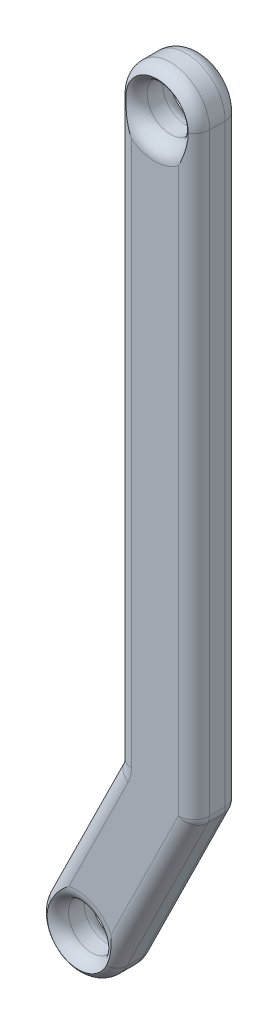
SolidWorks part; units mm, degrees
ref_plane "Front Plane" through (0, 0, 0) normal (0, 0, 1) x (1, 0, 0)
ref_plane "Top Plane" through (0, 0, 0) normal (0, 1, 0) x (1, 0, 0)
ref_plane "Right Plane" through (0, 0, 0) normal (1, 0, 0) x (0, 0, -1)
sketch "Sketch1" plane through (0, 0, 0) normal (0, 0, 1) x (1, 0, 0)
  line L0 (0, 0) -> (0, -37.72) construction
  line L1 (0, -37.72) -> (-5.0395, -47.9345) construction
  line L2 (-2.5, 0) -> (-2.5, -37.1369)
  line L3 (-2.5, -37.1369) -> (-7.2814, -46.8284)
  line L4 (2.5, 0) -> (2.5, -38.3031)
  line L5 (2.5, -38.3031) -> (-2.7975, -49.0406)
  circle A0 centre (0, 0) radius 1.5
  circle A1 centre (-5.0395, -47.9345) radius 1.5
  arc A2 (-2.5, 0) -> (2.5, 0) centre (0, 0) cw
  arc A3 (-7.2814, -46.8284) -> (-2.7975, -49.0406) centre (-5.0395, -47.9345) ccw
  dimension "D4" = 3
  dimension "D5" = 3
  dimension "D1" = 37.72
  dimension "D2" = 11.39
  dimension "D3" = 153.74
  dimension "D6" = 2.5
  dimension "D7" = 2.5
extrude "Boss-Extrude1" add sketch "Sketch1" along normal blind 3
fillet "Fillet1" radius 1 18 edges at (0, 2.5, 3) (0, 2.5, 0) (-2.5, -18.5684, 3) (-2.5, -18.5684, 0) (-2.5, -37.1369, 1.5) (-4.8907, -41.9826, 3) (-4.8907, -41.9826, 0) (-6.1456, -50.1765, 3) (-6.1456, -50.1765, 0) (-0.1487, -43.6719, 3) (-0.1487, -43.6719, 0) (2.5, -38.3031, 1.5) (2.5, -19.1516, 3) (2.5, -19.1516, 0) (1.5, 0, 0) (1.5, 0, 3) (-3.5395, -47.9345, 0) (-3.5395, -47.9345, 3)
